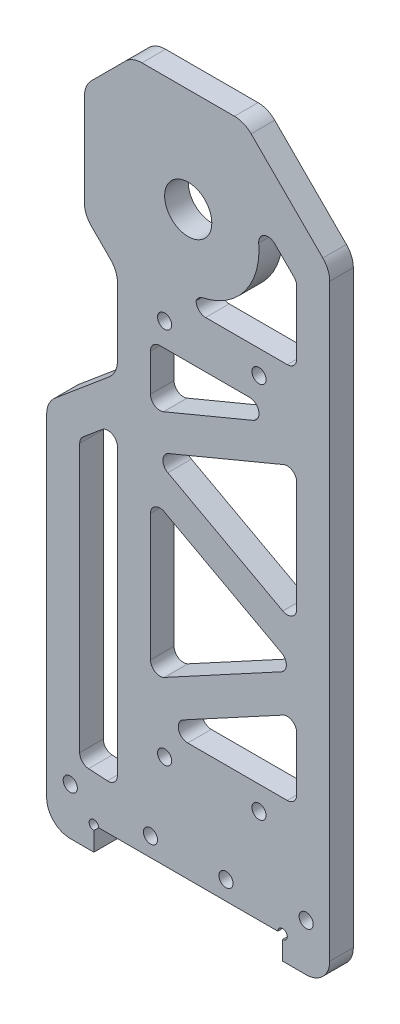
SolidWorks part; units mm, degrees
ref_plane "前视基准面" through (0, 0, 0) normal (0, 0, 1) x (1, 0, 0)
ref_plane "上视基准面" through (0, 0, 0) normal (0, 1, 0) x (1, 0, 0)
ref_plane "右视基准面" through (0, 0, 0) normal (1, 0, 0) x (0, 0, -1)
other "Configuration Table"
sketch "草图1" plane through (0, 0, 0) normal (0, 0, 1) x (1, 0, 0)
  line L1 (30, 0) -> (-30, 0)
  line L2 (30, 0) -> (30, 150)
  line L3 (30, 150) -> (-30, 150)
  line L4 (-30, 0) -> (-30, 150)
  point P6 (0, 0)
  dimension "D1" = 60
  dimension "D2" = 150
extrude "凸台-拉伸1" add sketch "草图1" along normal blind 5
sketch "草图2" plane through (0, 0, 5) normal (0, 0, 1) x (1, 0, 0)
  line L0 (-30, 0) -> (30, 0) construction
  line L1 (-20, 0) -> (20, 0)
  line L2 (-20, 0) -> (-20, 5)
  line L3 (-20, 5) -> (20, 5)
  line L4 (20, 0) -> (20, 5)
  line L5 (-25, 10) -> (25, 10) construction
  line L6 (-30, 150) -> (-30, 0) construction
  line L7 (30, 0) -> (30, 150) construction
  line L8 (-8, 9) -> (8, 9) construction
  line L9 (0, 0) -> (0, 9) construction
  circle A0 centre (-25, 10) radius 1.5
  circle A1 centre (25, 10) radius 1.5
  circle A2 centre (20, 5) radius 1
  circle A3 centre (-20, 5) radius 1
  circle A4 centre (8, 9) radius 1.5
  circle A5 centre (-8, 9) radius 1.5
  dimension "D1" = 3
  dimension "D3" = 2
  dimension "D10" = 3
  dimension "D2" = 5
  dimension "D4" = 10
  dimension "D5" = 10
  dimension "D6" = 5
  dimension "D7" = 5
  dimension "D8" = 10
  dimension "D9" = 16
  dimension "D11" = 4
extrude "切除-拉伸1" cut sketch "草图2" against normal blind 5
sketch "草图4" plane through (0, 0, 5) normal (0, 0, 1) x (1, 0, 0)
  line L0 (0, 0) -> (0, 150) construction
  line L1 (30, 150) -> (-30, 150) construction
  line L2 (-19, 5) -> (19, 5) construction
  circle A0 centre (0, 128) radius 5
  dimension "D2" = 10
  dimension "D5" = 123
extrude " pitch轴孔" cut sketch "草图4" against normal through all
sketch "草图5" plane through (0, 0, 5) normal (0, 0, 1) x (1, 0, 0)
  line L0 (-19.1511, 111.9303) -> (-15, 106.9832) construction
  line L1 (-30, 150) -> (-30, 0) construction
  line L2 (-15, 106.9832) -> (-15, 90.3497)
  line L3 (-15, 90.3497) -> (-30, 77.7632)
  line L4 (-30, 124.8595) -> (-19.1511, 111.9303) construction
  line L5 (30, 150) -> (-30, 150) construction
  line L6 (-30, 124.8595) -> (-30, 77.7632)
  line L7 (-30, 124.8595) -> (-30, 150)
  line L8 (-30, 150) -> (-11.8743, 150)
  line L9 (0, 128) -> (-19.1511, 111.9303) construction
  line L10 (-19.1511, 111.9303) -> (-65.3229, 73.1876) construction
  line L11 (-52.9813, 58.4796) -> (-30, 77.7632) construction
  line L12 (-65.3229, 73.1876) -> (-52.9813, 58.4796) construction
  line L13 (-11.8743, 150) -> (-22, 139.8743)
  line L14 (-22, 139.8743) -> (-22, 116.1257)
  line L15 (-22, 116.1257) -> (-15, 109.1257)
  line L16 (-15, 109.1257) -> (-15, 106.9832)
  line L17 (11.8743, 150) -> (30, 131.8743)
  line L18 (30, 0) -> (30, 150) construction
  line L19 (30, 131.8743) -> (30, 150)
  line L20 (30, 150) -> (11.8743, 150)
  arc A0 (-11.8743, 150) -> (-19.1511, 111.9303) centre (0, 128) ccw construction
  dimension "D1" = 40
  dimension "D2" = 25
  dimension "D3" = 15
  dimension "D4" = 30
  dimension "D5" = 19.2
  dimension "D6" = 135
  dimension "D7" = 135
  dimension "D8" = 45
extrude "切除-拉伸2" cut sketch "草图5" against normal through all
sketch "草图6" plane through (0, 0, 0) normal (0, 0, -1) x (-1, 0, 0)
  line L0 (19, 5) -> (-19, 5) construction
  line L1 (-15, 105) -> (5, 105) construction
  line L2 (-15, 105) -> (-15, 25) construction
  line L3 (-15, 25) -> (5, 25) construction
  line L4 (5, 105) -> (5, 25) construction
  line L5 (-15, 105) -> (5, 25) construction
  line L6 (-15, 25) -> (5, 105) construction
  line L7 (-30, 0) -> (-30, 131.8743) construction
  circle A0 centre (5, 105) radius 1.5
  circle A1 centre (-15, 105) radius 1.5
  circle A2 centre (-15, 25) radius 1.5
  circle A3 centre (5, 25) radius 1.5
  point P0 (-5, 65)
  dimension "D1" = 3
  dimension "D2" = 80
  dimension "D3" = 20
  dimension "D4" = 15
  dimension "D5" = 20
extrude "切除-拉伸3" cut sketch "草图6" against normal through all
sketch "草图7" plane through (0, 0, 5) normal (0, 0, 1) x (1, 0, 0)
  line L0 (-5, 105) -> (20, 105) construction
  line L1 (-8, 100) -> (23, 100)
  line L2 (10.6066, 138.6066) -> (23, 126.2132)
  line L3 (23, 100) -> (-8, 87.0855)
  line L4 (-8, 87.0855) -> (-8, 100)
  line L5 (23, 92.4169) -> (23, 62.712)
  line L6 (23, 62.712) -> (-8, 79.5024)
  line L7 (-8, 79.5024) -> (23, 92.4169)
  line L11 (-5, 25) -> (15, 25) construction
  line L12 (-8, 30) -> (23, 30)
  line L13 (23, 30) -> (23, 46.7904)
  line L14 (23, 46.7904) -> (-8, 30)
  line L15 (-10.2882, 23.9276) -> (-12.1028, 14.25)
  line L16 (-12.1028, 14.25) -> (-23, 14.891) construction
  line L21 (-5, 25) -> (-8, 9) construction
  line L22 (-25, 10) -> (-8, 9) construction
  line L23 (-30, 77.7632) -> (-30, 0) construction
  line L24 (-30, 77.7632) -> (-15, 90.3497) construction
  line L25 (30, 0) -> (30, 131.8743) construction
  line L26 (-15, 90.3497) -> (-15, 109.1257) construction
  line L27 (23, 126.2132) -> (23, 110)
  line L28 (23, 110) -> (1.2037, 110)
  line L29 (0, 128) -> (-5, 105) construction
  line L30 (1.2037, 110) -> (1.8817, 113.1185)
  line L31 (11.8743, 150) -> (30, 131.8743) construction
  line L32 (-8, 71.5416) -> (-8, 37.9608)
  line L33 (-8, 37.9608) -> (23, 54.7512)
  line L34 (23, 54.7512) -> (-8, 71.5416)
  line L35 (-15, 81.2118) -> (-23, 74.499)
  line L36 (-23, 74.499) -> (-23, 14.891)
  line L37 (-23, 14.891) -> (-15, 14.4204)
  line L38 (-15, 14.4204) -> (-15, 81.2118)
  line L39 (-8, 54.7512) -> (23, 54.7512) construction
  line L40 (-23, 74.499) -> (-15, 14.4204) construction
  circle A0 centre (0, 128) radius 15
  dimension "D1" = 30
  dimension "D18" = 5
  dimension "D4" = 5
  dimension "D5" = 5
  dimension "D6" = 7
  dimension "D7" = 7
  dimension "D10" = 5
  dimension "D11" = 7
  dimension "D12" = 7
  dimension "D13" = 7
  dimension "D14" = 7
  dimension "D15" = 7
  dimension "D2" = 5
  dimension "D3" = 7
  dimension "D16" = 7
  dimension "D17" = 5
  dimension "D19" = 7
  dimension "D20" = 7
  dimension "D21" = 7
extrude "切除-拉伸4" cut sketch "草图7" against normal through all contours L37 L38 L35 L36 | L33 L34 L32 | L13 L14 L12 | L7 L6 L5 | L4 L3 L1 | A0 L30 L28 L27 L2
fillet "圆角1" radius 2 21 edges at (23, 92.4169, 2.5) (23, 62.712, 2.5) (-8, 79.5024, 2.5) (10.6066, 138.6066, 2.5) (23, 126.2132, 2.5) (23, 110, 2.5) (1.2037, 110, 2.5) (1.8817, 113.1185, 2.5) (-8, 30, 2.5) (23, 46.7904, 2.5) (23, 30, 2.5) (-8, 71.5416, 2.5) (23, 54.7512, 2.5) (-8, 37.9608, 2.5) (-8, 100, 2.5) (23, 100, 2.5) (-8, 87.0855, 2.5) (-15, 81.2118, 2.5) (-15, 14.4204, 2.5) (-23, 14.891, 2.5) (-23, 74.499, 2.5)
fillet "圆角2" radius 5 10 edges at (-15, 90.3497, 2.5) (-15, 109.1257, 2.5) (-22, 116.1257, 2.5) (-22, 139.8743, 2.5) (-11.8743, 150, 2.5) (11.8743, 150, 2.5) (30, 131.8743, 2.5) (30, 0, 2.5) (-30, 77.7632, 2.5) (-30, 0, 2.5)
